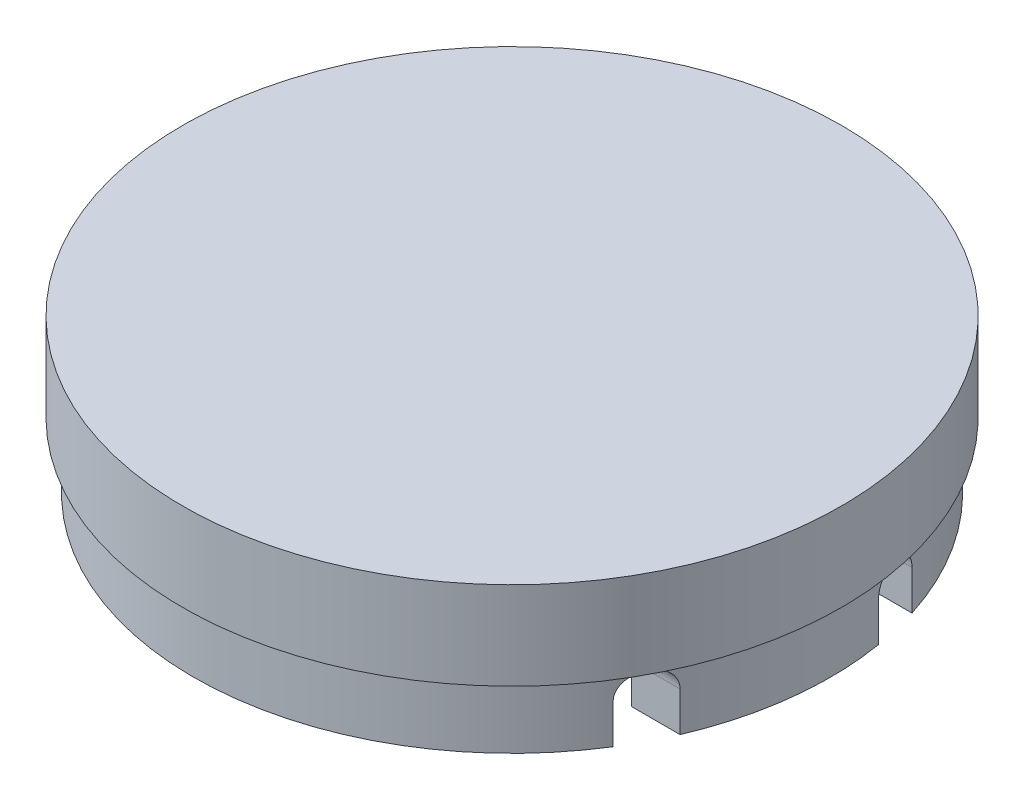
SolidWorks part; units mm, degrees
material "Polyethylene Cross-Linked"
ref_plane "Front Plane" through (0, 0, 0) normal (0, 0, 1) x (1, 0, 0)
ref_plane "Top Plane" through (0, 0, 0) normal (0, 1, 0) x (1, 0, 0)
ref_plane "Right Plane" through (0, 0, 0) normal (1, 0, 0) x (0, 0, -1)
sketch "Sketch1" plane through (0, 0, 0) normal (0, 0, 1) x (1, 0, 0)
  line L0 (0, 0) -> (0, 92.3285) construction
  line L1 (0, 0) -> (92.075, 0)
  line L2 (92.075, 0) -> (92.075, 19.05)
  line L3 (92.075, 19.05) -> (95.25, 19.05)
  line L4 (95.25, 19.05) -> (95.25, 44.45)
  line L5 (95.25, 44.45) -> (0, 44.45)
  line L6 (0, 44.45) -> (0, 0)
  dimension "D1" = 95.25
  dimension "D2" = 3.175
  dimension "D3" = 19.05
  dimension "D4" = 25.4
revolve "Revolve1" add sketch "Sketch1" angle 360 about L0
ref_plane "Plane1" through (0, 0, 101) normal (0, 0, 1) x (1, 0, 0)
ref_plane "Plane2" through (92.075, 0, 0) normal (1, 0, 0) x (0, 0, -1)
shell "Shell1" thickness 12.7 removed face at (0, 0, -92.075)
sketch "Sketch2" plane through (0, 0, 0) normal (1, 0, 0) x (0, 0, -1)
  line L0 (-42.4802, -11.43) -> (-42.4802, 11.43) construction
  line L1 (-92.075, 0) -> (92.075, 0) construction
  line L2 (-48.8302, -11.43) -> (-48.8302, 11.43)
  line L3 (-36.1302, -11.43) -> (-36.1302, 11.43)
  line L5 (21.4516, -11.43) -> (21.4516, 11.43) construction
  line L6 (15.1016, -11.43) -> (15.1016, 11.43)
  line L7 (27.8016, -11.43) -> (27.8016, 11.43)
  line L8 (-42.4802, -5.7006) -> (-42.4802, 27.8494) construction
  line L11 (21.4516, -4.583) -> (21.4516, 28.967) construction
  line L12 (-92.075, 19.05) -> (92.075, 19.05) construction
  arc A0 (-48.8302, -11.43) -> (-36.1302, -11.43) centre (-42.4802, -11.43) ccw
  arc A1 (-36.1302, 11.43) -> (-48.8302, 11.43) centre (-42.4802, 11.43) ccw
  arc A2 (15.1016, -11.43) -> (27.8016, -11.43) centre (21.4516, -11.43) ccw
  arc A3 (27.8016, 11.43) -> (15.1016, 11.43) centre (21.4516, 11.43) ccw
  point P4 (-42.4802, 0)
  point P10 (21.4516, 0)
  point P34 (-42.4802, 17.78)
  dimension "D2" = 1.27
  dimension "D1" = 12.7
  dimension "D3" = 12.7
extrude "Cut-Extrude2" cut sketch "Sketch2" along normal up to next
